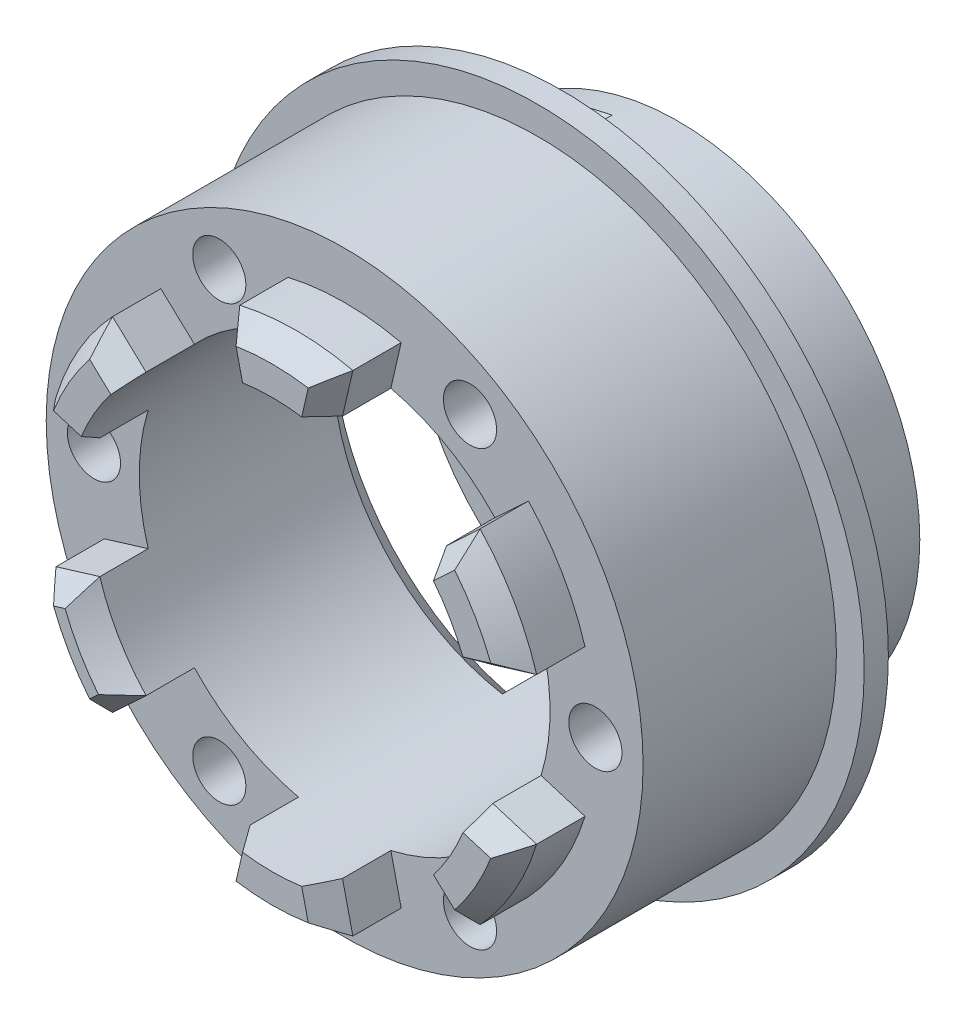
SolidWorks part; units mm, degrees
ref_plane "정면" through (0, 0, 0) normal (0, 0, 1) x (1, 0, 0)
ref_plane "윗면" through (0, 0, 0) normal (0, 1, 0) x (1, 0, 0)
ref_plane "우측면" through (0, 0, 0) normal (1, 0, 0) x (0, 0, -1)
sketch "스케치1" plane through (0, 0, 0) normal (0, 0, 1) x (1, 0, 0)
  circle A0 centre (0, 0) radius 10
  dimension "D1" = 20
extrude "보스-돌출1" add sketch "스케치1" along normal blind 2
sketch "스케치2" plane through (0, 0, 2) normal (0, 0, 1) x (1, 0, 0)
  circle A0 centre (0, 0) radius 10
  circle A1 centre (0, 0) radius 8.5
  circle A5 centre (0, 0) radius 10 construction
  dimension "D1" = 1.5
extrude "보스-돌출2" add sketch "스케치2" along normal blind 2.8
sketch "스케치4" plane through (0, 0, 4.8) normal (0, 0, 1) x (1, 0, 0)
  circle A0 centre (0, 0) radius 13.5
  circle A1 centre (0, 0) radius 8.5
  circle A2 centre (0, 0) radius 8.5 construction
  dimension "D1" = 27
extrude "보스-돌출3" add sketch "스케치4" along normal blind 1
sketch "스케치5" plane through (0, 0, 5.8) normal (0, 0, 1) x (1, 0, 0)
  circle A0 centre (0, 0) radius 8.5
  circle A1 centre (0, 0) radius 12.35
  circle A2 centre (0, 0) radius 8.5 construction
  dimension "D1" = 24.7
extrude "보스-돌출4" add sketch "스케치5" along normal blind 8
sketch "스케치6" plane through (0, 0, 13.8) normal (0, 0, 1) x (1, 0, 0)
  circle A0 centre (0, 0) radius 10.375 construction
  circle A6 centre (0, 0) radius 8.5 construction
  circle A8 centre (10.375, 0) radius 1.1
  circle A9 centre (5.1875, -8.985) radius 1.1
  circle A10 centre (-5.1875, -8.985) radius 1.1
  circle A11 centre (-10.375, 0) radius 1.1
  circle A12 centre (-5.1875, 8.985) radius 1.1
  circle A13 centre (5.1875, 8.985) radius 1.1
  point P19 (0, 0)
  point P20 (0, 0)
  dimension "D1" = 1.875
  dimension "D2" = 2.2
  dimension "D3" = 6
extrude "컷-돌출1" cut sketch "스케치6" against normal blind 8
sketch "스케치7" plane through (0, 0, 0) normal (0, 0, -1) x (-1, 0, 0)
  circle A0 centre (0, 0) radius 7 construction
  circle A5 centre (0, 0) radius 3
  circle A6 centre (-7, 0) radius 1.15
  circle A7 centre (7, 0) radius 1.15
  circle A9 centre (0, 7) radius 1.15
  circle A11 centre (0, -7) radius 1.15
  dimension "D1" = 14
  dimension "D2" = 2.3
  dimension "D4" = 6
extrude "컷-돌출2" cut sketch "스케치7" against normal through all
sketch "스케치10" plane through (0, 0, 13.8) normal (0, 0, 1) x (1, 0, 0)
  line L24 (2.3395, 10.1334) -> (1.9121, 8.2821)
  line L25 (-2.3395, 10.1334) -> (-1.9121, 8.2821)
  line L26 (7.6061, 7.0928) -> (6.2165, 5.797)
  line L27 (9.9456, 3.0407) -> (8.1286, 2.4852)
  line L28 (9.9456, -3.0407) -> (8.1286, -2.4852)
  line L29 (7.6061, -7.0928) -> (6.2165, -5.797)
  line L30 (2.3395, -10.1334) -> (1.9121, -8.2821)
  line L31 (-2.3395, -10.1334) -> (-1.9121, -8.2821)
  line L32 (-7.6061, -7.0928) -> (-6.2165, -5.797)
  line L33 (-9.9456, -3.0407) -> (-8.1286, -2.4852)
  line L34 (-9.9456, 3.0407) -> (-8.1286, 2.4852)
  line L35 (-7.6061, 7.0928) -> (-6.2165, 5.797)
  arc A0 (-7.6061, 7.0928) -> (-9.9456, 3.0407) centre (0, 0) ccw
  arc A1 (-8.1286, -2.4852) -> (-6.2165, -5.797) centre (0, 0) ccw
  arc A2 (2.3395, 10.1334) -> (-2.3395, 10.1334) centre (0, 0) ccw
  arc A3 (9.9456, 3.0407) -> (7.6061, 7.0928) centre (0, 0) ccw
  arc A4 (7.6061, -7.0928) -> (9.9456, -3.0407) centre (0, 0) ccw
  arc A5 (-2.3395, -10.1334) -> (2.3395, -10.1334) centre (0, 0) ccw
  arc A6 (-9.9456, -3.0407) -> (-7.6061, -7.0928) centre (0, 0) ccw
  arc A7 (-1.9121, -8.2821) -> (1.9121, -8.2821) centre (0, 0) ccw
  arc A8 (6.2165, -5.797) -> (8.1286, -2.4852) centre (0, 0) ccw
  arc A9 (8.1286, 2.4852) -> (6.2165, 5.797) centre (0, 0) ccw
  arc A10 (1.9121, 8.2821) -> (-1.9121, 8.2821) centre (0, 0) ccw
  arc A11 (-6.2165, 5.797) -> (-8.1286, 2.4852) centre (0, 0) ccw
  circle A12 centre (0, 0) radius 8.5 construction
  circle A13 centre (0, 0) radius 8.5 construction
  point P9 (0, 0)
  point P10 (0, 0)
  point P21 (0, 0)
  point P30 (0, 0)
  point P48 (0, 0)
  point P61 (0, 0)
  dimension "D1" = 1.9
  dimension "D4" = 6
extrude "보스-돌출5" add sketch "스케치10" along normal blind 3
chamfer "모따기1" distance 1 angle 35 19 edges at (-9.0067, -5.2, 16.8) (0, -10.4, 16.8) (9.0067, -5.2, 16.8) (9.0067, 5.2, 16.8) (0, 10.4, 16.8) (-9.0067, 5.2, 16.8) (-9.0371, -2.7629, 16.8) (-7.3612, -4.25, 16.8) (-6.9113, -6.4449, 16.8) (2.1258, -9.2078, 16.8) (-2.1258, -9.2078, 16.8) (6.9113, -6.4449, 16.8) (9.0371, -2.7629, 16.8) (9.0371, 2.7629, 16.8) (6.9113, 6.4449, 16.8) (2.1258, 9.2078, 16.8) (-2.1258, 9.2078, 16.8) (-9.0371, 2.7629, 16.8) (-6.9113, 6.4449, 16.8) first distance on face at (-8.8912, -5.1334, 15.3) first distance on face at (0, -10.2667, 15.3) first distance on face at (8.8912, -5.1334, 15.3) first distance on face at (8.8912, 5.1334, 15.3) first distance on face at (0, 10.2667, 15.3) first distance on face at (-8.8912, 5.1334, 15.3) first distance on face at (-9.0371, -2.7629, 15.3) first distance on face at (8.5, 0, 2) first distance on face at (-6.9113, -6.4449, 15.3) first distance on face at (2.1258, -9.2078, 15.3) first distance on face at (-2.1258, -9.2078, 15.3) first distance on face at (6.9113, -6.4449, 15.3) first distance on face at (9.0371, -2.7629, 15.3) first distance on face at (9.0371, 2.7629, 15.3) first distance on face at (6.9113, 6.4449, 15.3) first distance on face at (2.1258, 9.2078, 15.3) first distance on face at (-2.1258, 9.2078, 15.3) first distance on face at (-9.0371, 2.7629, 15.3) first distance on face at (-6.9113, 6.4449, 15.3)
sketch "스케치11" plane through (0, 0, 0) normal (0, 0, -1) x (-1, 0, 0)
  line L0 (0, 0) -> (1.7365, 9.8481)
  line L1 (0, 0) -> (1.7365, -9.8481)
  line L2 (0, 0) -> (10, 0) construction
  circle A0 centre (0, 0) radius 10
  circle M6 centre (7, 0) radius 1.15
  circle M9 centre (0, 0) radius 3
  circle M10 centre (0, 0) radius 10
  dimension "D1" = 80
  dimension "D2" = 80
extrude "컷-돌출3" cut sketch "스케치11" against normal blind 2.8 from offset 2 contours L2 A0 L0 M9 M6 | L2 L1 M9 M10 M6 region at (-4.961, 4.3448, 0) region at (-4.961, -4.3448, 0) offset against normal yes
chamfer "모따기2" distance 1 angle 45 2 edges at (-8.5, 0, 4.8) (-10, 0, 2)
